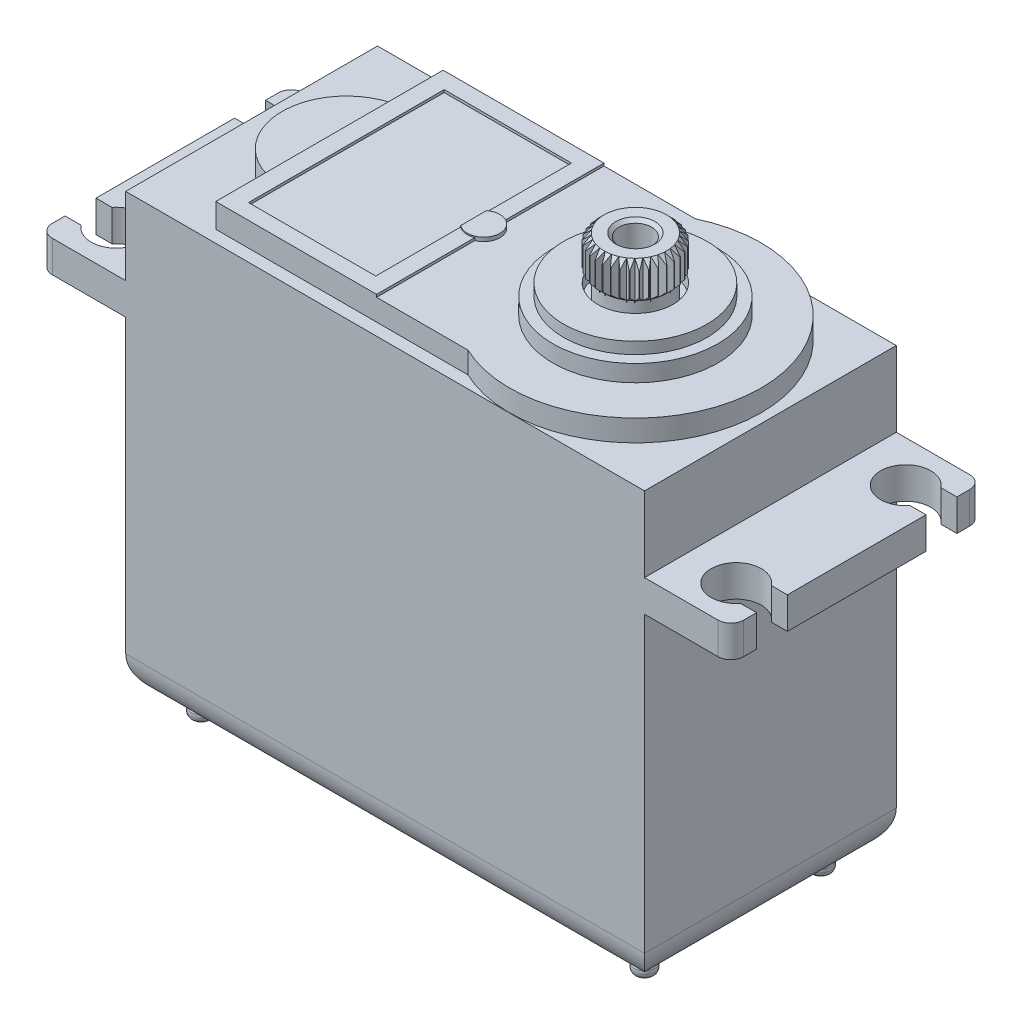
SolidWorks part; units mm, degrees
ref_plane "Front Plane" through (0, 0, 0) normal (0, 0, 1) x (1, 0, 0)
ref_plane "Top Plane" through (0, 0, 0) normal (0, 1, 0) x (1, 0, 0)
ref_plane "Right Plane" through (0, 0, 0) normal (1, 0, 0) x (0, 0, -1)
sketch "Sketch1" plane through (0, 0, 0) normal (0, 1, 0) x (1, 0, 0)
  line L1 (-18.6567, 11.3793) -> (21.6633, 11.3793)
  line L2 (-18.6567, 11.3793) -> (-18.6567, -8.1907)
  line L3 (-18.6567, -8.1907) -> (21.6633, -8.1907)
  line L4 (21.6633, 11.3793) -> (21.6633, -8.1907)
extrude "Boss-Extrude1" add sketch "Sketch1" along normal blind 35.37
sketch "Sketch2" plane through (21.6633, 0, 0) normal (1, 0, 0) x (0, 0, -1)
  line L0 (-8.1907, 0) -> (-8.1907, 3)
  line L1 (-8.1907, 35.37) -> (-8.1907, 0) construction
  line L2 (-8.1907, 3) -> (-5.1907, 0)
  line L3 (-8.1907, 0) -> (11.3793, 0) construction
  line L4 (-5.1907, 0) -> (-8.1907, 0)
  line L5 (1.5943, 0) -> (1.5943, 35.37) construction
  line L6 (-8.1907, 35.37) -> (11.3793, 35.37) construction
  line L7 (8.3793, 0) -> (11.3793, 0)
  line L8 (11.3793, 3) -> (8.3793, 0)
  line L9 (11.3793, 0) -> (11.3793, 3)
extrude "Cut-Extrude1" cut sketch "Sketch2" against normal up to next
sketch "Sketch3" plane through (0, 0, 8.1907) normal (0, 0, 1) x (1, 0, 0)
  line L0 (21.6633, 0) -> (18.6633, 0)
  line L1 (-18.6567, 0) -> (21.6633, 0) construction
  line L2 (18.6633, 0) -> (21.6633, 3)
  line L3 (21.6633, 35.37) -> (21.6633, 3) construction
  line L4 (21.6633, 3) -> (21.6633, 0)
  line L5 (1.5033, 35.37) -> (1.5033, 0) construction
  line L6 (-18.6567, 35.37) -> (21.6633, 35.37) construction
  line L7 (-18.6567, 3) -> (-18.6567, 0)
  line L8 (-15.6567, 0) -> (-18.6567, 3)
  line L9 (-18.6567, 0) -> (-15.6567, 0)
extrude "Cut-Extrude2" cut sketch "Sketch3" against normal up to next
fillet "Fillet2" radius 3 4 edges at (21.6633, 3, -1.5943) (1.5033, 3, 8.1907) (-18.6567, 3, -1.5943) (1.5033, 3, -11.3793)
sketch "Sketch5" plane through (21.6633, 0, 0) normal (1, 0, 0) x (0, 0, -1)
  line L0 (1.5943, 35.37) -> (1.5943, 29.53) construction
  line L1 (-8.1907, 35.37) -> (11.3793, 35.37) construction
  line L2 (-8.1907, 29.53) -> (1.5943, 29.53)
  line L3 (-8.1907, 35.37) -> (-8.1907, 4.2426) construction
  line L4 (1.5943, 29.53) -> (11.3793, 29.53)
  line L5 (11.3793, 35.37) -> (11.3793, 4.2426) construction
  line L6 (11.3793, 29.53) -> (11.3793, 27.07)
  line L7 (11.3793, 27.07) -> (-8.1907, 27.07)
  line L8 (-8.1907, 27.07) -> (-8.1907, 29.53)
extrude "Boss-Extrude2" add sketch "Sketch5" along normal blind 6.71
sketch "Sketch7" plane through (-18.6567, 0, 0) normal (-1, 0, 0) x (0, 0, 1)
  line L0 (-1.5943, 35.37) -> (-1.5943, 29.3613) construction
  line L1 (-11.3793, 29.3613) -> (-1.5943, 29.3613)
  line L2 (-1.5943, 29.3613) -> (8.1907, 29.3613)
  line L3 (8.1907, 29.3613) -> (8.1907, 26.9013)
  line L4 (8.1907, 26.9013) -> (-11.3793, 26.9013)
  line L5 (-11.3793, 26.9013) -> (-11.3793, 29.3613)
  line L6 (-11.3793, 35.37) -> (8.1907, 35.37) construction
  line L7 (8.1907, 35.37) -> (8.1907, 4.2426) construction
  line L8 (-11.3793, 35.37) -> (-11.3793, 4.2426) construction
extrude "Boss-Extrude3" add sketch "Sketch7" along normal blind 6.71
sketch "Sketch8" plane through (0, 29.53, 0) normal (0, 1, 0) x (1, 0, 0)
  line L0 (28.3733, 1.5943) -> (-25.3667, 1.5943) construction
  line L2 (-25.3667, -8.1907) -> (-25.3667, 11.3793) construction
  line L4 (28.3733, -3.7925) -> (27.1303, -3.7925)
  line L5 (28.3733, 11.3793) -> (28.3733, -8.1907) construction
  line L6 (28.3733, 8.181) -> (28.3733, 9.381)
  line L7 (28.3733, 9.381) -> (27.1303, 9.381)
  line L8 (28.3733, 8.181) -> (28.3733, 6.981)
  line L9 (28.3733, 6.981) -> (27.1303, 6.981)
  line L10 (28.3733, -4.9925) -> (28.3733, -3.7925)
  line L11 (28.3733, -6.1925) -> (27.1303, -6.1925)
  line L12 (28.3733, -4.9925) -> (28.3733, -6.1925)
  line L13 (1.5033, 11.3793) -> (1.5033, -8.1907) construction
  line L14 (21.6633, 11.3793) -> (-18.6567, 11.3793) construction
  line L15 (-18.6567, -8.1907) -> (21.6633, -8.1907) construction
  line L24 (-25.3667, 6.981) -> (-24.1237, 6.981)
  line L25 (-25.3667, -4.9925) -> (-25.3667, -6.1925)
  line L26 (-25.3667, -6.1925) -> (-24.1237, -6.1925)
  line L27 (-25.3667, -4.9925) -> (-25.3667, -3.7925)
  line L28 (-25.3667, -3.7925) -> (-24.1237, -3.7925)
  line L29 (-25.3667, 8.181) -> (-25.3667, 6.981)
  line L30 (-25.3667, 9.381) -> (-24.1237, 9.381)
  line L31 (-25.3667, 8.181) -> (-25.3667, 9.381)
  arc A0 (27.1303, -3.7925) -> (27.1303, -6.1925) centre (25.5933, -4.9925) ccw
  arc A1 (27.1303, 6.981) -> (27.1303, 9.381) centre (25.5933, 8.181) cw
  arc A4 (-24.1237, 6.981) -> (-24.1237, 9.381) centre (-22.5867, 8.181) ccw
  arc A5 (-24.1237, -3.7925) -> (-24.1237, -6.1925) centre (-22.5867, -4.9925) cw
extrude "Cut-Extrude3" cut sketch "Sketch8" against normal up to next
sketch "Sketch9" plane through (0, 35.37, 0) normal (0, 1, 0) x (1, 0, 0)
  line L0 (6.9933, -8.1907) -> (6.9933, -7.2426) construction
  line L1 (-18.6567, 6.4311) -> (-12.6067, 6.4311) construction
  line L2 (6.9933, 11.3793) -> (6.9933, 10.4311) construction
  line L3 (-18.6567, -3.2426) -> (-12.6067, -3.2426) construction
  line L4 (-18.6567, -8.1907) -> (-18.6567, 11.3793) construction
  line L5 (-18.6567, 1.5943) -> (21.6633, 1.5943) construction
  line L6 (-12.6067, 10.4311) -> (6.9933, 10.4311)
  line L7 (-18.6567, 11.3793) -> (-18.6567, -8.1907) construction
  line L8 (-12.6067, -7.2426) -> (-12.6067, -3.2426)
  line L9 (21.6633, -8.1907) -> (21.6633, 11.3793) construction
  line L10 (-12.6067, 10.4311) -> (-12.6067, 6.4311)
  line L11 (-12.6067, -7.2426) -> (6.9933, -7.2426)
  line L12 (21.6633, 1.5943) -> (20.9438, 1.5943) construction
  line L13 (21.6633, 11.3793) -> (-18.6567, 11.3793) construction
  arc A0 (6.9933, 10.4311) -> (6.9933, -7.2426) centre (11.1697, 1.5943) cw
  arc A1 (-12.6067, 6.4311) -> (-12.6067, -3.2426) centre (-11.2767, 1.5943) ccw
extrude "Boss-Extrude4" add sketch "Sketch9" along normal blind 1.67
sketch "Sketch10" plane through (0, 37.04, 0) normal (0, 1, 0) x (1, 0, 0)
  circle A1 centre (11.1697, 1.5943) radius 6.415
extrude "Boss-Extrude5" add sketch "Sketch10" along normal blind 1.3
sketch "Sketch11" plane through (0, 38.34, 0) normal (0, 1, 0) x (-1, 0, 0)
  circle A2 centre (-11.1697, -1.5943) radius 5.575
extrude "Boss-Extrude6" add sketch "Sketch11" along normal blind 0.9
sketch "Sketch12" plane through (0, 39.24, 0) normal (0, 1, 0) x (1, 0, 0)
  circle A1 centre (11.1697, 1.5943) radius 2.925
extrude "Cut-Extrude4" cut sketch "Sketch12" against normal blind 1
sketch "Sketch13" plane through (0, 38.24, 0) normal (0, 1, 0) x (-1, 0, 0)
  circle A0 centre (-11.1697, -1.5943) radius 2.425
extrude "Boss-Extrude7" add sketch "Sketch13" along normal blind 1.5
sketch "Sketch14" plane through (0, 39.74, 0) normal (0, 1, 0) x (1, 0, 0)
  circle A0 centre (11.1697, 1.5943) radius 2.925
extrude "Boss-Extrude8" add sketch "Sketch14" along normal blind 2.86
sketch "Sketch15" plane through (0, 42.6, 0) normal (0, 1, 0) x (1, 0, 0)
  circle A0 centre (11.1697, 1.5943) radius 1.27
extrude "Cut-Extrude5" cut sketch "Sketch15" against normal blind 7
sketch "Sketch16" plane through (0, 37.04, 0) normal (0, 1, 0) x (1, 0, 0)
  line L0 (-12.6067, -7.2426) -> (6.9933, -7.2426) construction
  line L1 (-12.6067, 10.4311) -> (-0.1067, 10.4311)
  line L2 (-12.6067, 10.4311) -> (-12.6067, -7.2426)
  line L3 (-12.6067, -7.2426) -> (-0.1067, -7.2426)
  line L4 (-0.1067, 10.4311) -> (-0.1067, -7.2426)
  line L5 (-6.3168, 9.1673) -> (-6.3567, 10.4311) construction
  line L6 (-11.2628, 9.1673) -> (-1.3708, 9.1673)
  line L7 (-11.2628, 9.1673) -> (-11.2628, -6.0433)
  line L8 (-11.2628, -6.0433) -> (-1.3708, -6.0433)
  line L9 (-1.3708, 9.1673) -> (-1.3708, 1.562)
  line L10 (-11.2628, 1.562) -> (-12.6067, 1.5943) construction
  line L11 (-1.3708, 1.562) -> (-0.1067, 1.5943) construction
  line L12 (-6.3168, -6.0433) -> (-6.3567, -7.2426) construction
  line L13 (-1.3708, 1.562) -> (-1.3708, -6.0433)
extrude "Boss-Extrude9" add sketch "Sketch16" along normal blind 0.2
sketch "Sketch17" plane through (0, 37.24, 0) normal (0, 1, 0) x (-1, 0, 0)
  line L0 (1.3708, -1.562) -> (1.3708, -2.562)
  line L1 (1.3708, 6.0433) -> (1.3708, -9.1673) construction
  line L2 (1.3708, -1.562) -> (1.3708, -0.562)
  arc A0 (1.3708, -2.562) -> (1.3708, -0.562) centre (0.592, -1.562) cw
extrude "Boss-Extrude10" add sketch "Sketch17" along normal blind 0.1 and the other way blind 0.5
sketch "Sketch19" plane through (0, 42.6, 0) normal (0, 1, 0) x (1, 0, 0)
  line L0 (10.8404, 4.5007) -> (11.3402, 4.5143) construction
  line L1 (11.3402, 4.5143) -> (11.0903, 4.0075)
  line L2 (11.0903, 4.0075) -> (10.8404, 4.5007)
  line L3 (11.0903, 4.5075) -> (11.0903, 4.0075) construction
  line L4 (10.8404, 4.5007) -> (10.7613, 4.6463)
  line L5 (11.3402, 4.5143) -> (11.4053, 4.6463)
  line L6 (10.7613, 4.6463) -> (11.4053, 4.6463)
  circle A3 centre (11.1697, 1.5943) radius 2.925 construction
  circle A4 centre (11.1697, 1.5943) radius 2.925 construction
extrude "Cut-Extrude11" cut sketch "Sketch19" against normal blind 3
sketch "Sketch21" plane through (0, 0, 0) normal (0, -1, 0) x (1, 0, 0)
  line L0 (1.5033, 5.1907) -> (1.5033, -8.3793) construction
  line L1 (20.7846, 7.3121) -> (17.7846, 7.3121)
  line L2 (20.7846, 7.3121) -> (20.7846, 4.3121)
  line L3 (20.7846, 4.3121) -> (17.7846, 4.3121)
  line L4 (17.7846, 7.3121) -> (17.7846, 4.3121)
  line L5 (-15.6567, 5.1907) -> (18.6633, 5.1907) construction
  line L6 (-15.6567, -8.3793) -> (18.6633, -8.3793) construction
  line L7 (-15.6567, -1.5943) -> (18.6633, -1.5943) construction
  line L8 (-15.6567, -8.3793) -> (-15.6567, 5.1907) construction
  line L9 (18.6633, -8.3793) -> (18.6633, 5.1907) construction
  line L10 (17.7846, -10.5006) -> (17.7846, -7.5006)
  line L11 (20.7846, -7.5006) -> (17.7846, -7.5006)
  line L12 (20.7846, -10.5006) -> (20.7846, -7.5006)
  line L13 (20.7846, -10.5006) -> (17.7846, -10.5006)
  line L14 (-17.778, -7.5006) -> (-14.778, -7.5006)
  line L15 (-14.778, -10.5006) -> (-14.778, -7.5006)
  line L16 (-14.778, 7.3121) -> (-14.778, 4.3121)
  line L17 (-17.778, 4.3121) -> (-14.778, 4.3121)
  line L18 (-17.778, -10.5006) -> (-14.778, -10.5006)
  line L19 (-17.778, -10.5006) -> (-17.778, -7.5006)
  line L20 (-17.778, 7.3121) -> (-17.778, 4.3121)
  line L21 (-17.778, 7.3121) -> (-14.778, 7.3121)
extrude "Cut-Extrude12" cut sketch "Sketch21" against normal blind 1
fillet "Fillet4" radius 1 4 edges at (-14.778, 0.5, -7.5006) (-14.778, 0.5, 4.3121) (17.7846, 0.5, -7.5006) (17.7846, 0.5, 4.3121)
fillet "Fillet5" radius 1 4 edges at (-25.3667, 28.1313, 8.1907) (-25.3667, 28.1313, -11.3793) (28.3733, 28.3, -11.3793) (28.3733, 28.3, 8.1907)
chamfer "Chamfer2" distance 0.5 angle 45 2 edges at (11.2493, 42.6, 1.3297) (11.2493, 39.74, 1.3297)
chamfer "Chamfer3" distance 0.25 angle 45 1 edges at (11.1697, 42.6, -0.3243)
pattern_circular "CirPattern12" count 34 over 360 about axis through (11.1697, 42.6, -1.5943) along (0, -1, 0) of "Cut-Extrude11"
sketch "Sketch23" plane through (0, 1, 0) normal (0, -1, 0) x (1, 0, 0)
  line L0 (1.5033, 5.1907) -> (1.5033, -8.3793) construction
  line L1 (-14.7854, 5.1907) -> (17.792, 5.1907) construction
  line L2 (-14.7854, -8.3793) -> (17.792, -8.3793) construction
  line L3 (18.6633, -1.5943) -> (-15.6567, -1.5943) construction
  line L4 (18.6633, -7.508) -> (18.6633, 4.3195) construction
  line L5 (-15.6567, -7.508) -> (-15.6567, 4.3195) construction
  circle A0 centre (18.7344, -8.4503) radius 0.4237
  circle A1 centre (18.7344, 5.2618) radius 0.4237
  circle A2 centre (-15.7278, 5.2618) radius 0.4237
  circle A3 centre (-15.7278, -8.4503) radius 0.4237
extrude "Boss-Extrude12" add sketch "Sketch23" along normal blind 0.1
sketch "Sketch24" plane through (0, 0.9, 0) normal (0, -1, 0) x (1, 0, 0)
  line L0 (1.5033, 5.1907) -> (1.5033, -8.3793) construction
  line L1 (-14.7854, 5.1907) -> (17.792, 5.1907) construction
  line L2 (-14.7854, -8.3793) -> (17.792, -8.3793) construction
  line L3 (18.6633, -1.5943) -> (-15.6567, -1.5943) construction
  line L4 (18.6633, -7.508) -> (18.6633, 4.3195) construction
  line L5 (-15.6567, -7.508) -> (-15.6567, 4.3195) construction
  circle A0 centre (18.7344, -8.4503) radius 0.8
  circle A1 centre (18.7344, 5.2618) radius 0.8
  circle A2 centre (-15.7278, 5.2618) radius 0.8
  circle A3 centre (-15.7278, -8.4503) radius 0.8
extrude "Boss-Extrude13" add sketch "Sketch24" along normal blind 0.9
fillet "Fillet8" radius 0.45 4 edges at (18.7344, 0, -9.2503) (-15.7278, 0, -7.6503) (-15.7278, 0, 4.4618) (18.7344, 0, 6.0618)
fillet "Fillet9" radius 0.2 4 edges at (-15.7278, 0.9, -7.6503) (-15.7278, 0.9, 4.4618) (18.7344, 0.9, 6.0618) (18.7344, 0.9, -9.2503)
sketch "Sketch25" plane through (0, 0, 0) normal (0, -1, 0) x (1, 0, 0)
  line L0 (18.0844, 5.3868) -> (18.0844, 5.1368)
  line L1 (18.6094, 4.6118) -> (18.8594, 4.6118)
  line L2 (18.0844, 5.3868) -> (18.6094, 5.3868)
  line L3 (18.6094, 5.3868) -> (18.6094, 5.9118)
  line L4 (19.3844, 5.1368) -> (19.3844, 5.3868)
  line L5 (18.8594, 5.9118) -> (18.6094, 5.9118)
  line L6 (1.5033, 5.1907) -> (1.5033, -8.3793) construction
  line L7 (-14.7854, 5.1907) -> (17.792, 5.1907) construction
  line L8 (-14.7854, -8.3793) -> (17.792, -8.3793) construction
  line L9 (18.6633, -1.5943) -> (-15.6567, -1.5943) construction
  line L10 (18.6633, -7.508) -> (18.6633, 4.3195) construction
  line L11 (-15.6567, -7.508) -> (-15.6567, 4.3195) construction
  line L12 (18.6094, -8.3253) -> (18.0844, -8.3253)
  line L13 (18.6094, -7.8003) -> (18.6094, -8.3253)
  line L14 (18.8594, -8.3253) -> (18.8594, -7.8003)
  line L15 (19.3844, -8.3253) -> (18.8594, -8.3253)
  line L16 (18.8594, -8.5753) -> (19.3844, -8.5753)
  line L17 (18.8594, 5.9118) -> (18.8594, 5.3868)
  line L18 (18.8594, 5.3868) -> (19.3844, 5.3868)
  line L19 (18.8594, -9.1003) -> (18.8594, -8.5753)
  line L20 (19.3844, 5.1368) -> (18.8594, 5.1368)
  line L21 (18.8594, 5.1368) -> (18.8594, 4.6118)
  line L22 (18.8594, -9.1003) -> (18.6094, -9.1003)
  line L23 (18.6094, 4.6118) -> (18.6094, 5.1368)
  line L24 (18.6094, 5.1368) -> (18.0844, 5.1368)
  line L25 (19.3844, -8.3253) -> (19.3844, -8.5753)
  line L26 (18.6094, -8.5753) -> (18.6094, -9.1003)
  line L27 (18.0844, -8.5753) -> (18.6094, -8.5753)
  line L28 (18.6094, -7.8003) -> (18.8594, -7.8003)
  line L29 (18.0844, -8.5753) -> (18.0844, -8.3253)
  line L30 (-15.0778, -8.5753) -> (-15.0778, -8.3253)
  line L31 (-15.6028, -7.8003) -> (-15.8528, -7.8003)
  line L32 (-15.0778, -8.5753) -> (-15.6028, -8.5753)
  line L33 (-15.6028, -8.5753) -> (-15.6028, -9.1003)
  line L34 (-16.3778, -8.3253) -> (-16.3778, -8.5753)
  line L35 (-15.6028, 5.1368) -> (-15.0778, 5.1368)
  line L36 (-15.6028, 4.6118) -> (-15.6028, 5.1368)
  line L37 (-15.8528, -9.1003) -> (-15.6028, -9.1003)
  line L38 (-15.8528, 5.1368) -> (-15.8528, 4.6118)
  line L39 (-16.3778, 5.1368) -> (-15.8528, 5.1368)
  line L40 (-15.8528, -9.1003) -> (-15.8528, -8.5753)
  line L41 (-15.8528, 5.3868) -> (-16.3778, 5.3868)
  line L42 (-15.8528, 5.9118) -> (-15.8528, 5.3868)
  line L43 (-15.8528, -8.5753) -> (-16.3778, -8.5753)
  line L44 (-16.3778, -8.3253) -> (-15.8528, -8.3253)
  line L45 (-15.8528, -8.3253) -> (-15.8528, -7.8003)
  line L46 (-15.6028, -7.8003) -> (-15.6028, -8.3253)
  line L47 (-15.6028, -8.3253) -> (-15.0778, -8.3253)
  line L48 (-15.8528, 5.9118) -> (-15.6028, 5.9118)
  line L49 (-16.3778, 5.1368) -> (-16.3778, 5.3868)
  line L50 (-15.6028, 5.3868) -> (-15.6028, 5.9118)
  line L51 (-15.0778, 5.3868) -> (-15.6028, 5.3868)
  line L52 (-15.6028, 4.6118) -> (-15.8528, 4.6118)
  line L53 (-15.0778, 5.3868) -> (-15.0778, 5.1368)
extrude "Cut-Extrude14" cut sketch "Sketch25" against normal blind 0.6
